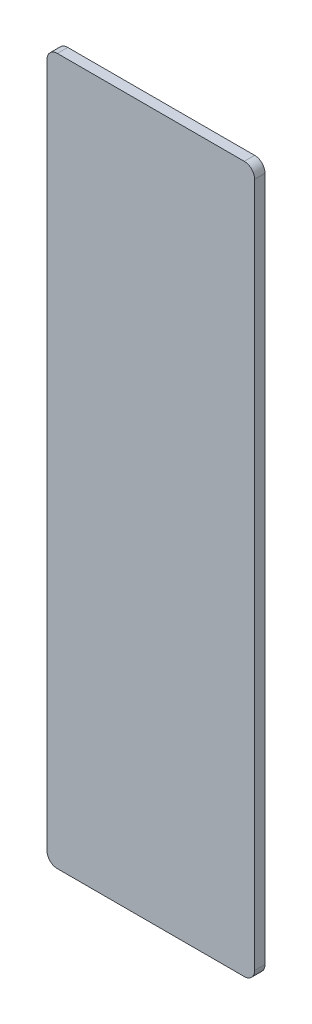
SolidWorks part; units mm, degrees
ref_plane "前视基准面" through (0, 0, 0) normal (0, 0, 1) x (1, 0, 0)
ref_plane "上视基准面" through (0, 0, 0) normal (0, 1, 0) x (1, 0, 0)
ref_plane "右视基准面" through (0, 0, 0) normal (1, 0, 0) x (0, 0, -1)
sketch "草图1" plane through (0, 0, 0) normal (0, 0, 1) x (1, 0, 0)
  line L1 (39.0403, 19.6595) -> (49.0403, 19.6595)
  line L2 (39.0403, 19.6595) -> (39.0403, -14.3405)
  line L3 (39.0403, -14.3405) -> (49.0403, -14.3405)
  line L4 (49.0403, 19.6595) -> (49.0403, -14.3405)
  point P4 (52.8947, 17.7751)
  point P6 (42.8947, -16.2249)
extrude "凸台-拉伸1" add sketch "草图1" along normal blind 0.5
fillet "圆角1" radius 0.5 4 edges at (49.0403, 19.6595, 0.25) (49.0403, -14.3405, 0.25) (39.0403, -14.3405, 0.25) (39.0403, 19.6595, 0.25)
sketch "草图2" plane through (0, 0, 0) normal (0, 0, -1) x (-1, 0, 0)
  line L0 (-49.0403, -13.8405) -> (-49.0403, 19.1595) construction
  line L1 (-48.0409, 16.6339) -> (-47.0409, 16.6339)
  line L2 (-48.0409, 16.6339) -> (-48.0409, -11.2777)
  line L3 (-48.0409, -11.2777) -> (-47.0409, -11.2777)
  line L4 (-47.0409, 16.6339) -> (-47.0409, -11.2777)
  line L5 (-39.0403, 19.1595) -> (-39.0403, -13.8405) construction
  line L6 (-41.0403, 16.6339) -> (-40.0403, 16.6339)
  line L7 (-41.0403, 16.6339) -> (-41.0403, 1.6595)
  line L8 (-41.0403, 1.6595) -> (-40.0403, 1.6595)
  line L9 (-40.0403, 16.6339) -> (-40.0403, 1.6595)
  line L10 (-39.5403, -14.3405) -> (-48.5403, -14.3405) construction
  line L11 (-47.0409, 18.6595) -> (-41.0403, 18.6595)
  line L12 (-47.0409, 18.6595) -> (-47.0409, 17.6595)
  line L13 (-47.0409, 17.6595) -> (-41.0403, 17.6595)
  line L14 (-41.0403, 18.6595) -> (-41.0403, 17.6595)
  line L15 (-46.9113, -12.3405) -> (-41.2308, -12.3405)
  line L16 (-46.9113, -12.3405) -> (-46.9113, -13.3405)
  line L17 (-46.9113, -13.3405) -> (-41.2308, -13.3405)
  line L18 (-41.2308, -12.3405) -> (-41.2308, -13.3405)
  line L19 (-48.5403, 19.6595) -> (-39.5403, 19.6595) construction
  dimension "D1" = 0.9994
  dimension "D2" = 1
  dimension "D3" = 1
  dimension "D4" = 1
  dimension "D5" = 1
  dimension "D6" = 1
  dimension "D7" = 1
  dimension "D8" = 1
  dimension "D9" = 15
extrude "凸台-拉伸2" add sketch "草图2" along normal blind 1
sketch "草图3" plane through (0, -13.3405, 0) normal (0, -1, 0) x (1, 0, 0)
  line L1 (41.2308, -0.5) -> (46.9113, -0.5)
  line L2 (41.2308, -0.5) -> (41.2308, -1)
  line L3 (41.2308, -1) -> (46.9113, -1)
  line L4 (46.9113, -0.5) -> (46.9113, -1)
  line L5 (46.9113, -1) -> (41.2308, -1) construction
  dimension "D1" = 0.5
extrude "凸台-拉伸3" add sketch "草图3" along normal blind 0.5
sketch "草图4" plane through (40.0403, 0, 0) normal (-1, 0, 0) x (0, 0, 1)
  line L0 (-1, 16.6339) -> (0, 16.6339) construction
  line L1 (-0.5, 16.6339) -> (-1, 16.6339)
  line L2 (-0.5, 16.6339) -> (-0.5, 1.6595)
  line L3 (-0.5, 1.6595) -> (-1, 1.6595)
  line L4 (-1, 16.6339) -> (-1, 1.6595)
  dimension "D1" = 0.5
extrude "凸台-拉伸4" add sketch "草图4" along normal blind 0.5
sketch "草图5" plane through (0, 18.6595, 0) normal (0, 1, 0) x (1, 0, 0)
  line L0 (41.0403, 1) -> (41.0403, 0) construction
  line L1 (41.0403, 1) -> (47.0409, 1)
  line L2 (41.0403, 1) -> (41.0403, 0.5)
  line L3 (41.0403, 0.5) -> (47.0409, 0.5)
  line L4 (47.0409, 1) -> (47.0409, 0.5)
  line L5 (41.0403, 1) -> (47.0409, 1) construction
  dimension "D1" = 0.5
extrude "凸台-拉伸5" add sketch "草图5" along normal blind 0.5
sketch "草图6" plane through (48.0409, 0, 0) normal (1, 0, 0) x (0, 0, -1)
  line L1 (1, 16.6339) -> (0.5, 16.6339)
  line L2 (1, 16.6339) -> (1, -11.2777)
  line L3 (1, -11.2777) -> (0.5, -11.2777)
  line L4 (0.5, 16.6339) -> (0.5, -11.2777)
  line L8 (1, 16.6339) -> (1, -11.2777) construction
  dimension "D1" = 0.5
extrude "凸台-拉伸6" add sketch "草图6" along normal blind 0.5
chamfer "倒角1" distance 0.5 angle 45 4 edges at (44.0711, -13.8405, -1) (48.5409, 2.6781, -1) (44.0406, 19.1595, -1) (39.5403, 9.1467, -1)
